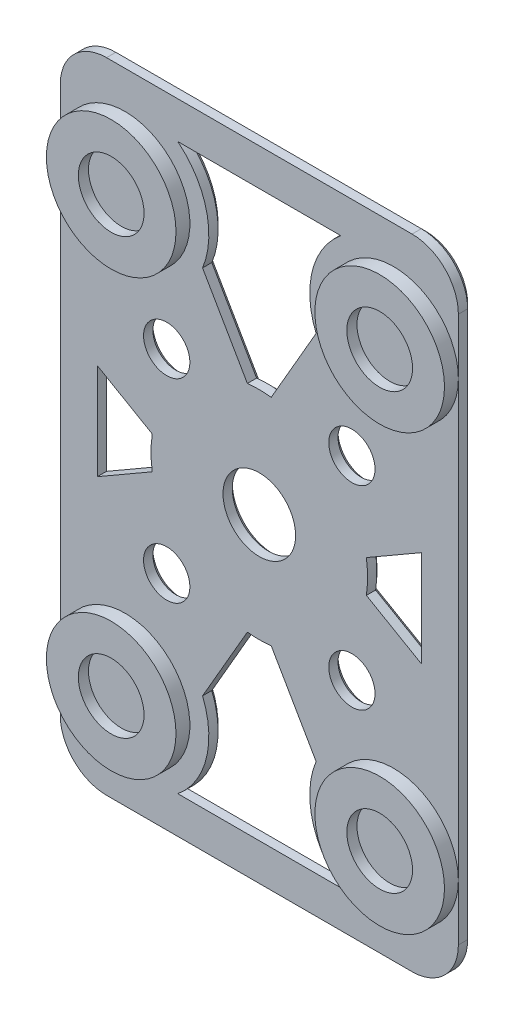
SolidWorks part; units mm, degrees
ref_plane "Alzado" through (0, 0, 0) normal (0, 0, 1) x (1, 0, 0)
ref_plane "Planta" through (0, 0, 0) normal (0, 1, 0) x (1, 0, 0)
ref_plane "Vista lateral" through (0, 0, 0) normal (1, 0, 0) x (0, 0, -1)
sketch "Croquis1" plane through (0, 0, 0) normal (0, 0, 1) x (1, 0, 0)
  line L1 (0, 0) -> (43, 0)
  line L2 (0, 0) -> (0, 69)
  line L3 (0, 69) -> (43, 69)
  line L4 (43, 0) -> (43, 69)
  dimension "D1" = 43
  dimension "D2" = 69
extrude "Saliente-Extruir1" add sketch "Croquis1" along normal blind 1.5
sketch "Croquis2" plane through (0, 0, 1.5) normal (0, 0, 1) x (1, 0, 0)
  line L0 (7, 57.965) -> (36, 57.965) construction
  line L1 (43, 69) -> (0, 69) construction
  line L2 (36, 57.965) -> (36, 11.035) construction
  line L3 (43, 0) -> (43, 69) construction
  circle A0 centre (7, 57.965) radius 7
  circle A1 centre (36, 57.965) radius 7
  circle A2 centre (7, 11.035) radius 7
  circle A3 centre (36, 11.035) radius 7
  point P8 (21.5, 57.965)
  point P11 (21.5, 69)
  point P12 (36, 34.5)
  point P15 (43, 34.5)
  dimension "D1" = 14
  dimension "D2" = 29
  dimension "D3" = 46.93
extrude "Saliente-Extruir2" add sketch "Croquis2" along normal blind 1.5
sketch "Croquis3" plane through (0, 0, 0) normal (0, 0, -1) x (-1, 0, 0)
  circle A0 centre (-7, 57.965) radius 5.05
  circle A1 centre (-36, 57.965) radius 5.05
  circle A2 centre (-7, 11.035) radius 5.05
  circle A3 centre (-36, 11.035) radius 5.05
  dimension "D1" = 10.1
extrude "Cortar-Extruir1" cut sketch "Croquis3" against normal blind 1.5
sketch "Croquis4" plane through (0, 0, 3) normal (0, 0, 1) x (1, 0, 0)
  circle A0 centre (7, 57.965) radius 3.55
  circle A1 centre (36, 57.965) radius 3.55
  circle A2 centre (7, 11.035) radius 3.55
  circle A3 centre (36, 11.035) radius 3.55
  dimension "D1" = 7.1
extrude "Cortar-Extruir2" cut sketch "Croquis4" against normal through all
sketch "Croquis5" plane through (0, 0, 1.5) normal (0, 0, -1) x (-1, 0, 0)
  circle A0 centre (-36, 57.965) radius 3.55
  circle A1 centre (-7, 57.965) radius 3.55
  circle A2 centre (-36, 11.035) radius 3.55
  circle A3 centre (-7, 11.035) radius 3.55
extrude "Saliente-Extruir3" add sketch "Croquis5" against normal blind 0.4
fillet "Redondeo1" radius 5 4 edges at (0, 69, 0.75) (0, 0, 0.75) (43, 0, 0.75) (43, 69, 0.75)
sketch "Croquis6" plane through (0, 0, 0) normal (0, 0, -1) x (-1, 0, 0)
  line L0 (-43, 5) -> (-43, 64) construction
  line L1 (-5, 0) -> (-38, 0) construction
  line L2 (-36, 11.035) -> (-14.465, 11.035) construction
  line L3 (-7, 11.035) -> (-7, 57.965) construction
  line L4 (-7, 57.965) -> (-36, 57.965) construction
  line L5 (-36, 57.965) -> (-36, 11.035) construction
  line L6 (0, 64) -> (0, 5) construction
  line L7 (-22.7888, 22.8727) -> (-27.6326, 14.483)
  line L8 (-30.3069, 4) -> (-12.6931, 4)
  line L9 (-38, 69) -> (-5, 69) construction
  line L10 (-20.2112, 46.1273) -> (-15.3674, 54.517)
  line L11 (-12.6931, 65) -> (-30.3069, 65)
  line L12 (-27.6326, 54.517) -> (-22.7888, 46.1273)
  line L13 (-33.064, 36.269) -> (-39, 39.6962)
  line L14 (-39, 39.6962) -> (-39, 29.3038)
  line L15 (-39, 29.3038) -> (-33.064, 32.731)
  line L16 (-9.936, 32.731) -> (-4, 29.3038)
  line L17 (-4, 29.3038) -> (-4, 39.6962)
  line L18 (-4, 39.6962) -> (-9.936, 36.269)
  line L19 (-38, 69) -> (-5, 69) construction
  line L20 (-15.3674, 14.483) -> (-20.2112, 22.8727)
  line L21 (-13.3767, 11.035) -> (-7, 11.035) construction
  line L22 (-9.315, 4) -> (-13.3767, 11.035) [skipped]
  line L23 (-5, 0) -> (-38, 0) construction
  line L24 (-43, 11.035) -> (-43, 57.965) construction
  line L25 (0, 57.965) -> (0, 11.035) construction
  circle A0 centre (-21.5, 11.035) radius 7.035 construction
  arc A1 (-22.7888, 22.8727) -> (-20.2112, 22.8727) centre (-21.5, 34.5) ccw
  circle A2 centre (-21.5, 57.965) radius 7.035 construction
  circle A3 centre (-36, 34.5) radius 3 construction
  circle A4 centre (-7, 34.5) radius 3 construction
  arc A5 (-9.936, 32.731) -> (-9.936, 36.269) centre (-21.5, 34.5) ccw
  arc A6 (-20.2112, 46.1273) -> (-22.7888, 46.1273) centre (-21.5, 34.5) ccw
  arc A7 (-33.064, 36.269) -> (-33.064, 32.731) centre (-21.5, 34.5) ccw
  circle A8 centre (-21.5, 34.5) radius 3.9211
  circle A9 centre (-31.5, 45) radius 2.5
  circle A10 centre (-36, 11.035) radius 9.05
  arc A11 (-30.3069, 4) -> (-27.6326, 14.483) centre (-36, 11.035) ccw
  circle A12 centre (-11.5, 45) radius 2.5
  circle A13 centre (-7, 11.035) radius 9.05
  arc A14 (-15.3674, 14.483) -> (-12.6931, 4) centre (-7, 11.035) ccw
  circle A15 centre (-11.5, 24) radius 2.5
  circle A16 centre (-7, 57.965) radius 9.05
  arc A17 (-12.6931, 65) -> (-7, 48.915) centre (-7, 57.965) ccw
  circle A18 centre (-31.5, 24) radius 2.5
  circle A19 centre (-36, 57.965) radius 9.05
  arc A20 (-27.6326, 54.517) -> (-30.3069, 65) centre (-36, 57.965) ccw
  point P5 (-43, 34.5)
  point P8 (-21.5, 0)
  dimension "D9" = 5
  dimension "D1" = 4
  dimension "D2" = 4
  dimension "D3" = 4
  dimension "D4" = 4
  dimension "D10" = 24
  dimension "D11" = 24
  dimension "D12" = 11.5
  dimension "D13" = 11.5
  dimension "D5" = 4
  dimension "D6" = 4
  dimension "D7" = 4
  dimension "D8" = 4
extrude "Cortar-Extruir3" cut sketch "Croquis6" against normal through all contours A14 L20 A1 L7 A11 L8 | A7 L13 L14 L15 | A5 L16 L17 L18 | A20 L12 A6 L10 A17 L11 | A9 | A18 | A12 | A15 | A8 region at (21.5, 11.7625, 0) region at (21.5, 57.2375, 0) region at (36.5451, 34.5, 0) region at (6.4549, 34.5, 0)
chamfer "Chaflán1" distance 0.5 angle 45 37 edges at (21.5, 46.1986, 0) (17.7893, 50.3222, 0) (15.7691, 60.2021, 0) (21.5, 65, 0) (27.2309, 60.2021, 0) (25.2107, 50.3222, 0) (4, 34.5, 0) (6.968, 37.9826, 0) (9.8014, 34.5, 0) (6.968, 31.0174, 0) (39, 34.5, 0) (36.032, 31.0174, 0) (33.1986, 34.5, 0) (36.032, 37.9826, 0) (21.5, 22.8014, 0) (25.2107, 18.6778, 0) (27.2309, 8.7979, 0) (21.5, 4, 0) (15.7691, 8.7979, 0) (17.7893, 18.6778, 0) (1.4645, 1.4645, 0) (21.5, 0, 0) (41.5355, 1.4645, 0) (43, 34.5, 0) (41.5355, 67.5355, 0) (21.5, 69, 0) (1.4645, 67.5355, 0) (0, 34.5, 0) (1.95, 57.965, 0) (30.95, 11.035, 0) (1.95, 11.035, 0) (30.95, 57.965, 0) (29, 45, 0) (17.5789, 34.5, 0) (9, 24, 0) (9, 45, 0) (29, 24, 0)
equation "\"D3@Croquis6\"=\"D2@Croquis6\""
equation "\"D4@Croquis6\"=\"D1@Croquis6\""
equation "\"D11@Croquis6\"=\"D10@Croquis6\""
equation "\"D13@Croquis6\"=\"D12@Croquis6\""
